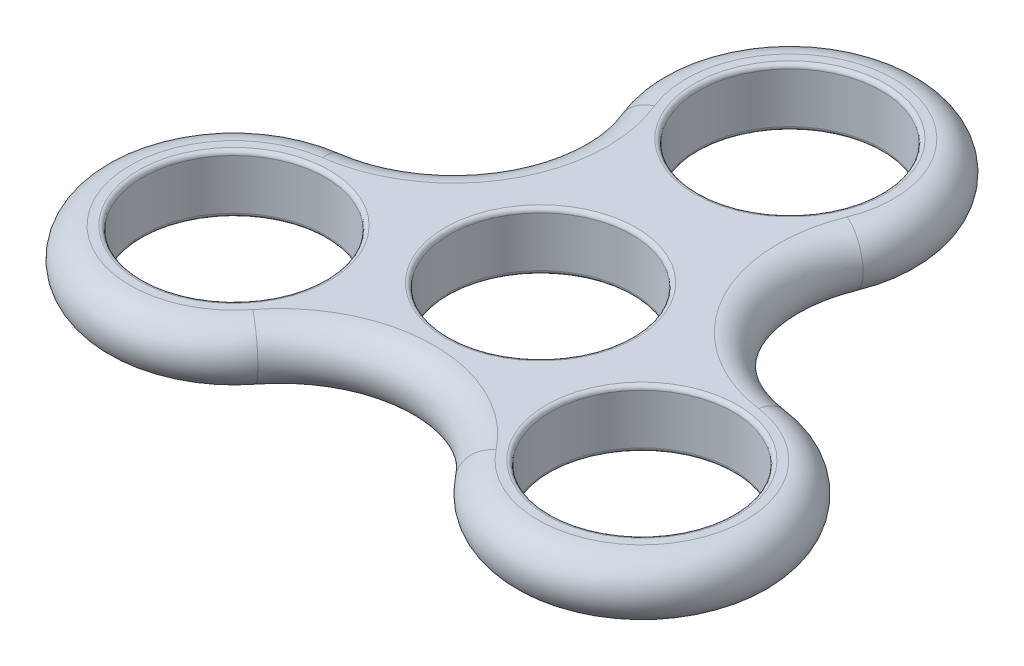
SolidWorks part; units mm, degrees
ref_plane "Front Plane" through (0, 0, 0) normal (0, 0, 1) x (1, 0, 0)
ref_plane "Top Plane" through (0, 0, 0) normal (0, 1, 0) x (1, 0, 0)
ref_plane "Right Plane" through (0, 0, 0) normal (1, 0, 0) x (0, 0, -1)
sketch "Sketch1" plane through (0, 0, 0) normal (0, 1, 0) x (1, 0, 0)
  circle A0 centre (0, 0) radius 11
  circle A1 centre (0, 30) radius 11
  circle A2 centre (24.5702, -12.3809) radius 11
  circle A3 centre (-24.4178, -12.4688) radius 11
  circle A4 centre (0, 30) radius 16
  circle A5 centre (-24.4178, -12.4688) radius 16
  circle A6 centre (24.5702, -12.3809) radius 16
  arc A7 (-14.8033, 23.9286) -> (-26.6184, 3.3791) centre (-28.6814, 18.2366) cw
  arc A8 (14.825, 23.9817) -> (26.7138, 3.4749) centre (28.7234, 18.3396) ccw
  arc A9 (-11.7582, -22.2531) -> (11.9457, -22.2106) centre (0.1103, -31.4259) cw
  point P12 (0.0508, 1.7168)
  dimension "D1" = 30
  dimension "D2" = 22
  dimension "D5" = 15
  dimension "D6" = 15
  dimension "D7" = 15
  dimension "D4" = 5
  dimension "D3" = 3
extrude "Boss-Extrude1" add sketch "Sketch1" along normal mid plane 7 contours A5 A9 A6 A8 A4 A7 A0 | A5 A3 | A6 A2 | A4 A1 region at (15.2593, 0, -27.0208) region at (0.03, 0, -13.2942) region at (-14.2081, 0, 0.7435) region at (36.2772, 0, 2.1501)
fillet "Fillet1" 2 edges at (-38.2599, 3.5, 20.4937) (-38.2599, -3.5, 20.4937) type full round first side face at (0, 3.5, 11) second side face at (0, -3.5, 11) middle face at (-28.7241, 0, 14.9653)
fillet "Fillet2" radius 0.5 6 edges at (-24.4178, -3.5, 23.4688) (-24.4178, 3.5, 23.4688) (24.5702, -3.5, 23.3809) (24.5702, 3.5, 23.3809) (0, -3.5, -19) (0, 3.5, -19)
fillet "Fillet3" radius 0.5 2 edges at (0, -3.5, 11) (0, 3.5, 11)
